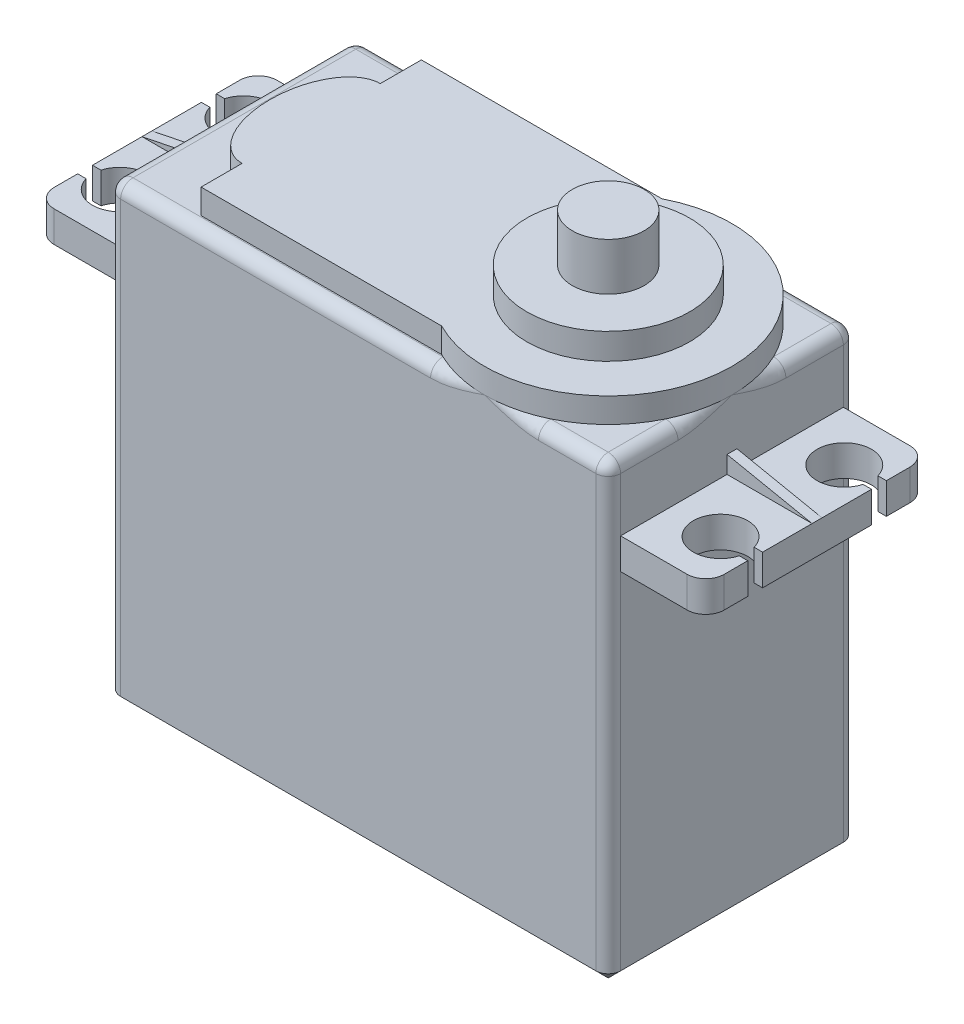
SolidWorks part; units mm, degrees
ref_plane "Plano frontal" through (0, 0, 0) normal (0, 0, 1) x (1, 0, 0)
ref_plane "Plano superior" through (0, 0, 0) normal (0, 1, 0) x (1, 0, 0)
ref_plane "Plano direito" through (0, 0, 0) normal (1, 0, 0) x (0, 0, -1)
sketch "Esboço1" plane through (0, 0, 0) normal (0, 1, 0) x (1, 0, 0)
  line L1 (20.2, 10) -> (-20.2, 10)
  line L2 (20.2, 10) -> (20.2, -10)
  line L3 (20.2, -10) -> (-20.2, -10)
  line L4 (-20.2, 10) -> (-20.2, -10)
  line L5 (20.2, 10) -> (-20.2, -10) construction
  line L6 (20.2, -10) -> (-20.2, 10) construction
  point P0 (0, 0)
  dimension "D1" = 40.4
  dimension "D2" = 20
extrude "Ressalto-extrusão1" add sketch "Esboço1" along normal blind 28.62
sketch "Esboço2" plane through (0, 28.62, 0) normal (0, 1, 0) x (1, 0, 0)
  line L4 (-27.075, -4.4) -> (-27.075, 4.4)
  line L6 (-27.075, 5.6) -> (-26.3916, 5.6)
  line L7 (-27.075, 5.6) -> (-27.075, 10)
  line L9 (20.2, 10) -> (-27.075, 10)
  line L11 (-27.075, 4.4) -> (-26.3916, 4.4)
  line L12 (-27.075, -4.4) -> (-26.3916, -4.4)
  line L13 (20.2, -10) -> (-27.075, -10)
  line L14 (-27.075, -5.6) -> (-27.075, -10)
  line L15 (-27.075, -5.6) -> (-26.3916, -5.6)
  line L16 (27.075, -5.6) -> (26.3916, -5.6)
  line L17 (27.075, -5.6) -> (27.075, -10)
  line L18 (20.2, -10) -> (27.075, -10)
  line L19 (27.075, -4.4) -> (26.3916, -4.4)
  line L20 (27.075, 4.4) -> (26.3916, 4.4)
  line L21 (20.2, 10) -> (27.075, 10)
  line L22 (27.075, 5.6) -> (27.075, 10)
  line L23 (27.075, 5.6) -> (26.3916, 5.6)
  line L25 (27.075, -4.4) -> (27.075, 4.4)
  arc A0 (-26.3916, 4.4) -> (-26.3916, 5.6) centre (-24.275, 5) ccw
  arc A1 (-26.3916, -4.4) -> (-26.3916, -5.6) centre (-24.275, -5) cw
  arc A2 (26.3916, -4.4) -> (26.3916, -5.6) centre (24.275, -5) ccw
  arc A3 (26.3916, 4.4) -> (26.3916, 5.6) centre (24.275, 5) cw
  point P0 (0, 0)
  dimension "D3" = 4.4
extrude "Ressalto-extrusão2" add sketch "Esboço2" along normal blind 2.5
sketch "Esboço3" plane through (0, 31.12, 0) normal (0, 1, 0) x (1, 0, 0)
  line L1 (20.2, 10) -> (-20.2, 10)
  line L2 (20.2, 10) -> (20.2, -10)
  line L3 (20.2, -10) -> (-20.2, -10)
  line L4 (-20.2, 10) -> (-20.2, -10)
extrude "Ressalto-extrusão3" add sketch "Esboço3" along normal blind 5.68
sketch "Esboço4" plane through (0, 36.8, 0) normal (0, 1, 0) x (1, 0, 0)
  line L0 (-13.8, -8.9) -> (-13.8, -5.5851)
  line L1 (-13.8, 5.5851) -> (-13.8, 8.9)
  line L3 (5.6404, 8.9) -> (-13.8, 8.9)
  line L4 (5.6404, -8.9) -> (-13.8, -8.9)
  arc A0 (5.6404, -8.9) -> (5.6404, 8.9) centre (10.2, 0) ccw
  ellipse E0 centre (-13.8, 0) end of major axis (-13.8, -5.5851) minor radius 3.3419 (-13.8, 5.5851) -> (-13.8, -5.5851) ccw
  dimension "D4" = 17.8
extrude "Ressalto-extrusão4" add sketch "Esboço4" along normal blind 2
sketch "Esboço5" plane through (0, 38.8, 0) normal (0, 1, 0) x (1, 0, 0)
  circle A0 centre (10.2, 0) radius 6.575
  dimension "D1" = 13.15
extrude "Ressalto-extrusão5" add sketch "Esboço5" along normal blind 2.1
sketch "Esboço6" plane through (0, 40.9, 0) normal (0, 1, 0) x (1, 0, 0)
  circle A0 centre (10.2, 0) radius 2.9
  dimension "D1" = 5.8
extrude "Ressalto-extrusão6" add sketch "Esboço6" along normal blind 3.84
sketch "Esboço7" plane through (0, 31.12, 0) normal (0, 1, 0) x (1, 0, 0)
  line L0 (-27.075, 0) -> (27.075, 0) construction
  line L1 (-27.075, 4.4) -> (-27.075, -4.4) construction
  line L2 (27.075, -4.4) -> (27.075, 4.4) construction
  line L4 (-27.075, -0.4) -> (27.075, -0.4)
  line L5 (-27.075, -0.4) -> (-27.075, 0.4)
  line L6 (-27.075, 0.4) -> (27.075, 0.4)
  line L7 (27.075, -0.4) -> (27.075, 0.4)
  line L8 (-27.075, -0.4) -> (27.075, 0.4) construction
  line L9 (-27.075, 0.4) -> (27.075, -0.4) construction
  point P6 (0, 0)
  dimension "D1" = 0.8
extrude "Ressalto-extrusão7" add sketch "Esboço7" along normal blind 5
sketch "Esboço8" plane through (0, 0, -0.4) normal (0, 0, -1) x (-1, 0, 0)
  line L0 (29.1385, 36.12) -> (29.1385, 31.12)
  line L1 (-20.2, 36.12) -> (-29.1385, 36.12)
  line L2 (-27.075, 31.12) -> (-20.2, 32.65)
  line L3 (20.2, 32.65) -> (20.2, 36.12)
  line L4 (-27.075, 31.12) -> (-29.1385, 31.12)
  line L5 (0, 0) -> (0, 47.0586) construction
  line L6 (-20.2, 32.65) -> (-20.2, 36.12)
  line L7 (27.075, 31.12) -> (29.1385, 31.12)
  line L8 (-29.1385, 36.12) -> (-29.1385, 31.12)
  line L9 (27.075, 31.12) -> (20.2, 32.65)
  line L10 (20.2, 36.12) -> (29.1385, 36.12)
extrude "Corte-extrusão1" cut sketch "Esboço8" against normal blind 4 and the other way blind 3
sketch "Esboço11" plane through (0, 28.62, 0) normal (0, -1, 0) x (1, 0, 0)
  line L1 (29.7209, -11.1851) -> (20.2, -11.1851)
  line L2 (29.7209, -11.1851) -> (29.7209, 12.2196)
  line L3 (29.7209, 12.2196) -> (20.2, 12.2196)
  line L4 (20.2, -11.1851) -> (20.2, 12.2196)
  line L5 (-20.2, 14.5525) -> (-29.1233, 14.5525)
  line L6 (-20.2, 14.5525) -> (-20.2, -12.8919)
  line L7 (-20.2, -12.8919) -> (-29.1233, -12.8919)
  line L8 (-29.1233, 14.5525) -> (-29.1233, -12.8919)
extrude "Corte-extrusão2" cut sketch "Esboço11" against normal blind 10
ref_plane "Plano2" through (0, 28.94, 0) normal (0, 1, 0) x (1, 0, 0)
sketch "Esboço12" plane through (0, 28.94, 0) normal (0, 1, 0) x (1, 0, 0)
  line L0 (-27.075, 0) -> (27.075, 0) construction
  line L1 (27.075, 5.6) -> (26.3916, 5.6)
  line L2 (-27.075, 9) -> (-27.075, 5.6)
  line L3 (27.075, 9) -> (27.075, 5.6)
  line L5 (20.2, 9) -> (20.2, -9)
  line L9 (-20.2, 9) -> (-20.2, -9)
  line L10 (27.075, 4.4) -> (26.3916, 4.4)
  line L11 (27.075, -4.4) -> (26.3916, -4.4)
  line L12 (27.075, -5.6) -> (26.3916, -5.6)
  line L13 (-26.3916, -5.6) -> (-27.075, -5.6)
  line L14 (-26.3916, -4.4) -> (-27.075, -4.4)
  line L15 (-27.075, -5.6) -> (-27.075, -9)
  line L16 (-27.075, 4.4) -> (-27.075, -4.4)
  line L17 (27.075, 4.4) -> (27.075, -4.4)
  line L18 (27.075, -5.6) -> (27.075, -9)
  line L19 (-27.075, 0.4) -> (-20.2, 0.4)
  line L20 (27.075, 0.4) -> (20.2, 0.4)
  line L21 (27.075, 0.4) -> (27.075, -0.4)
  line L22 (27.075, -0.4) -> (20.2, -0.4)
  line L23 (20.2, 0.4) -> (20.2, -0.4)
  line L24 (-20.2, -0.4) -> (-27.075, -0.4)
  line L25 (-26.3916, 4.4) -> (-27.075, 4.4)
  line L26 (-26.3916, 5.6) -> (-27.075, 5.6)
  line L27 (27.075, -9) -> (20.2, -9)
  line L28 (-27.075, 9) -> (-20.2, 9)
  line L29 (27.075, 9) -> (20.2, 9)
  line L30 (-27.075, -9) -> (-20.2, -9)
  arc A0 (26.3916, 5.6) -> (26.3916, 4.4) centre (24.275, 5) ccw
  arc A1 (26.3916, -4.4) -> (26.3916, -5.6) centre (24.275, -5) ccw
  arc A2 (-26.3916, 4.4) -> (-26.3916, 5.6) centre (-24.275, 5) ccw
  arc A3 (-26.3916, -4.4) -> (-26.3916, -5.6) centre (-24.275, -5) cw
extrude "Ressalto-extrusão8" add sketch "Esboço12" along normal blind 2.5 contours A0 L1 L3 L5 L20 L17 L10 | L5 L0 L17 L20 | A1 L11 L17 L22 L5 L18 L12 | L0 L23 L22 L21 | A2 L25 L16 L19 L9 L26 | L0 L16 L24 L9 | L16 L0 L9 L19 | L14 A3 L13 L15 L9 L24 L16 region at (-23.6375, 28.94, -0.2) region at (23.6375, 28.94, -0.2) region at (23.6375, 28.94, 0.2) region at (-23.6375, 28.94, 0.2) region at (-26.9649, 28.94, -2.4) region at (-23.6375, 28.94, 0.5101) region at (20.3101, 28.94, -4.7) region at (23.6375, 28.94, 0.5101)
sketch "Esboço13" plane through (0, 31.44, 0) normal (0, 1, 0) x (1, 0, 0)
  line L1 (27.075, 0.4) -> (20.2, 0.4)
  line L2 (27.075, 0.4) -> (27.075, -0.4)
  line L3 (27.075, -0.4) -> (20.2, -0.4)
  line L4 (20.2, 0.4) -> (20.2, -0.4)
  line L5 (-20.2, 0.4) -> (-27.075, 0.4)
  line L6 (-20.2, 0.4) -> (-20.2, -0.4)
  line L7 (-20.2, -0.4) -> (-27.075, -0.4)
  line L8 (-27.075, 0.4) -> (-27.075, -0.4)
extrude "Ressalto-extrusão9" add sketch "Esboço13" along normal blind 1.4
sketch "Esboço14" plane through (0, 0, 0.4) normal (0, 0, 1) x (1, 0, 0)
  line L0 (-27.075, 31.44) -> (-27.075, 32.84)
  line L1 (-27.075, 32.84) -> (-20.2, 32.84)
  line L2 (27.075, 31.44) -> (20.2, 32.84)
  line L3 (27.075, 31.44) -> (27.075, 32.84)
  line L4 (27.075, 32.84) -> (20.2, 32.84)
  line L11 (-27.075, 31.44) -> (-20.2, 32.84)
extrude "Corte-extrusão3" cut sketch "Esboço14" against normal blind 1.5 and the other way blind 1
fillet "Filete1" radius 1.5 4 edges at (-27.075, 30.19, -9) (-27.075, 30.19, 9) (27.075, 30.19, 9) (27.075, 30.19, -9)
fillet "Filete2" radius 1 7 edges at (20.2, 36.8, -5) (15.2, 36.8, -10) (15.2, 36.8, 10) (20.2, 36.8, 5) (-20.2, 36.8, 0) (-5, 36.8, -10) (-5, 36.8, 10)
fillet "Filete3" radius 1 8 edges at (-19.9071, 36.5071, -9.7071) (-19.9071, 36.5071, 9.7071) (19.9071, 36.5071, -9.7071) (19.9071, 36.5071, 9.7071) (-20.2, 17.9, -10) (-20.2, 17.9, 10) (20.2, 17.9, -10) (20.2, 17.9, 10)
chamfer "Chanfro1" distance 1 angle 45 8 edges at (-19.9071, 0, -9.7071) (-20.2, 0, 0) (-19.9071, 0, 9.7071) (0, 0, 10) (19.9071, 0, 9.7071) (20.2, 0, 0) (19.9071, 0, -9.7071) (0, 0, -10)
